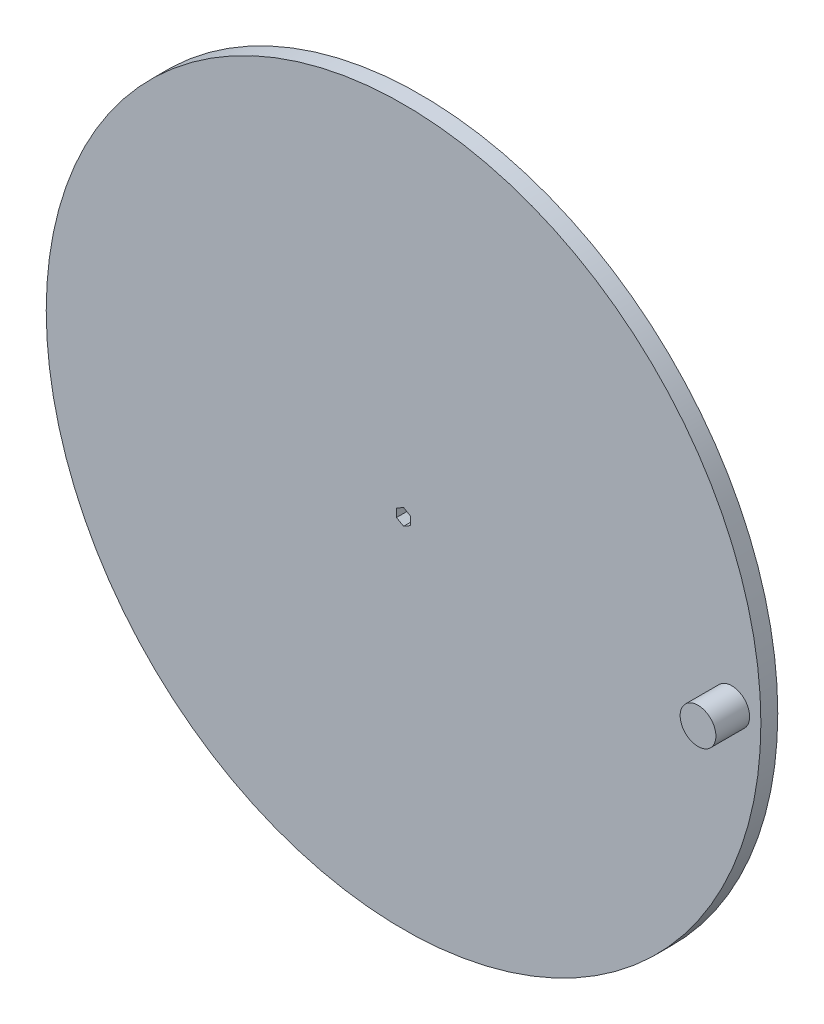
SolidWorks part; units mm, degrees
ref_plane "Front Plane" through (0, 0, 0) normal (0, 0, 1) x (1, 0, 0)
ref_plane "Top Plane" through (0, 0, 0) normal (0, 1, 0) x (1, 0, 0)
ref_plane "Right Plane" through (0, 0, 0) normal (1, 0, 0) x (0, 0, -1)
sketch "Sketch1" plane through (0, 0, 0) normal (0, 0, 1) x (1, 0, 0)
  circle A0 centre (0, 0) radius 63.5
extrude "Boss-Extrude1" add sketch "Sketch1" along normal blind 3
sketch "Sketch3" plane through (0, 0, 3) normal (0, 0, 1) x (1, 0, 0)
  circle A3 centre (58.325, 0) radius 3.175
  dimension "D1" = 58.325
extrude "Boss-Extrude2" add sketch "Sketch3" along normal blind 6
sketch "Sketch4" plane through (0, 0, 3) normal (0, 0, 1) x (1, 0, 0)
  line L1 (0, 1.4434) -> (-1.25, 0.7217)
  line L2 (-1.25, 0.7217) -> (-1.25, -0.7217)
  line L3 (-1.25, -0.7217) -> (0, -1.4434)
  line L4 (0, -1.4434) -> (1.25, -0.7217)
  line L5 (1.25, -0.7217) -> (1.25, 0.7217)
  line L6 (1.25, 0.7217) -> (0, 1.4434)
  circle A0 centre (0, 0) radius 1.25 construction
  dimension "D1" = 2.5
extrude "Cut-Extrude1" cut sketch "Sketch4" against normal blind 6
sketch "Sketch5" plane through (0, 0, 0) normal (0, 0, -1) x (-1, 0, 0)
  line L0 (-1.25, 0.7217) -> (0, 1.4434)
  line L1 (0, 1.4434) -> (1.25, 0.7217)
  line L2 (1.25, 0.7217) -> (1.25, -0.7217)
  line L3 (1.25, -0.7217) -> (0, -1.4434)
  line L4 (1.25, -0.7217) -> (0, -1.4434) construction
  line L5 (0, -1.4434) -> (-1.25, -0.7217)
  line L6 (-1.25, -0.7217) -> (-1.25, 0.7217)
  circle A0 centre (0, 0) radius 2.5
extrude "Boss-Extrude3" add sketch "Sketch5" along normal blind 6.5
fillet "Fillet1" radius 10 1 edges at (2.5, 0, 0)
sketch "Sketch6" plane through (0, 0, 3) normal (0, 0, 1) x (1, 0, 0)
  line L0 (0, 0) -> (58.325, 0)
